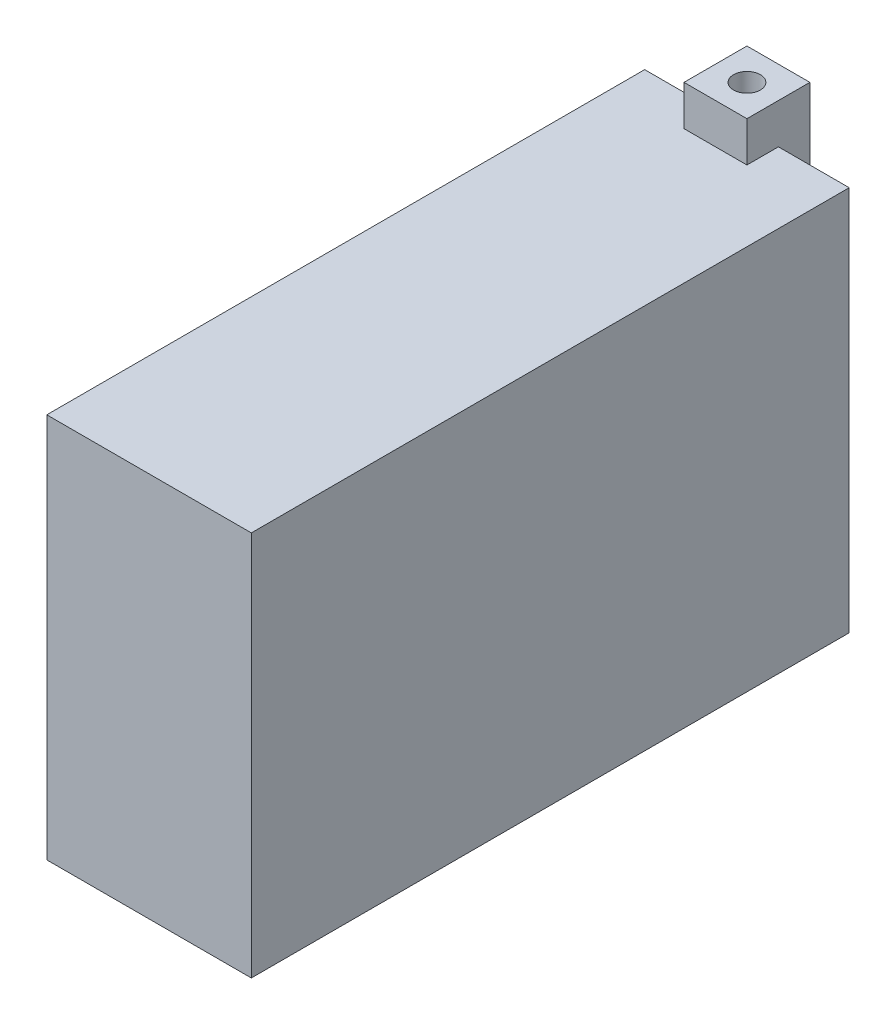
SolidWorks part; units mm, degrees
ref_plane "Спереди" through (0, 0, 0) normal (0, 0, 1) x (1, 0, 0)
ref_plane "Сверху" through (0, 0, 0) normal (0, 1, 0) x (1, 0, 0)
ref_plane "Справа" through (0, 0, 0) normal (1, 0, 0) x (0, 0, -1)
other "Configuration Table"
sketch "Эскиз1" plane through (0, 0, 0) normal (1, 0, 0) x (0, 0, -1)
  line L1 (-190, -122.5) -> (190, -122.5)
  line L2 (-190, -122.5) -> (-190, 122.5)
  line L3 (-190, 122.5) -> (190, 122.5)
  line L4 (190, -122.5) -> (190, 122.5)
  line L5 (-190, -122.5) -> (190, 122.5) construction
  line L6 (-190, 122.5) -> (190, -122.5) construction
  point P0 (0, 0)
  dimension "D1" = 380
  dimension "D2" = 245
extrude "Бобышка-Вытянуть1" add sketch "Эскиз1" along normal blind 65 and the other way blind 65
sketch "Эскиз2" plane through (0, -122.5, -67.5) normal (0, 1, 0) x (-1, 0, 0)
  line L0 (65, -122.5) -> (-65, -122.5) construction
  line L1 (-20, -122.5) -> (20, -122.5)
  line L2 (-20, -122.5) -> (-20, -102.5)
  line L3 (-20, -102.5) -> (20, -102.5)
  line L4 (20, -122.5) -> (20, -102.5)
  line L5 (0, 73.1391) -> (0, -235.5852) construction
  dimension "D1" = 40
  dimension "D2" = 20
  dimension "D3" = 20
extrude "Бобышка-Вытянуть2" add sketch "Эскиз2" against normal blind 25.5
sketch "Эскиз3" plane through (0, 67.5, -190) normal (0, 0, 1) x (1, 0, 0)
  line L0 (-20, -215.5) -> (20, -215.5)
  line L1 (-20, -215.5) -> (-20, -155.5)
  line L2 (20, -215.5) -> (20, -155.5)
  line L3 (-20, -155.5) -> (20, -155.5)
  dimension "D1" = 60
extrude "Бобышка-Вытянуть3" add sketch "Эскиз3" against normal blind 20
mirror "Зеркальное отражение1" about plane through (0, 0, 0) normal (0, 1, 0) of "Бобышка-Вытянуть2", "Бобышка-Вытянуть3"
sketch "Эскиз4" plane through (0, -148, 0) normal (0, -1, 0) x (-1, 0, 0)
  line L0 (0, 170) -> (0, 210) construction
  line L1 (20, 170) -> (-20, 170) construction
  line L2 (20, 210) -> (-20, 210) construction
  line L5 (20, 190) -> (-20, 190) construction
  line L6 (20, 210) -> (20, 170) construction
  circle A0 centre (0, 190) radius 8.5
  dimension "D1" = 17
extrude "Вырез-Вытянуть1" cut sketch "Эскиз4" against normal up to surface (296 mm away) up to face at (0, 148, -190)
